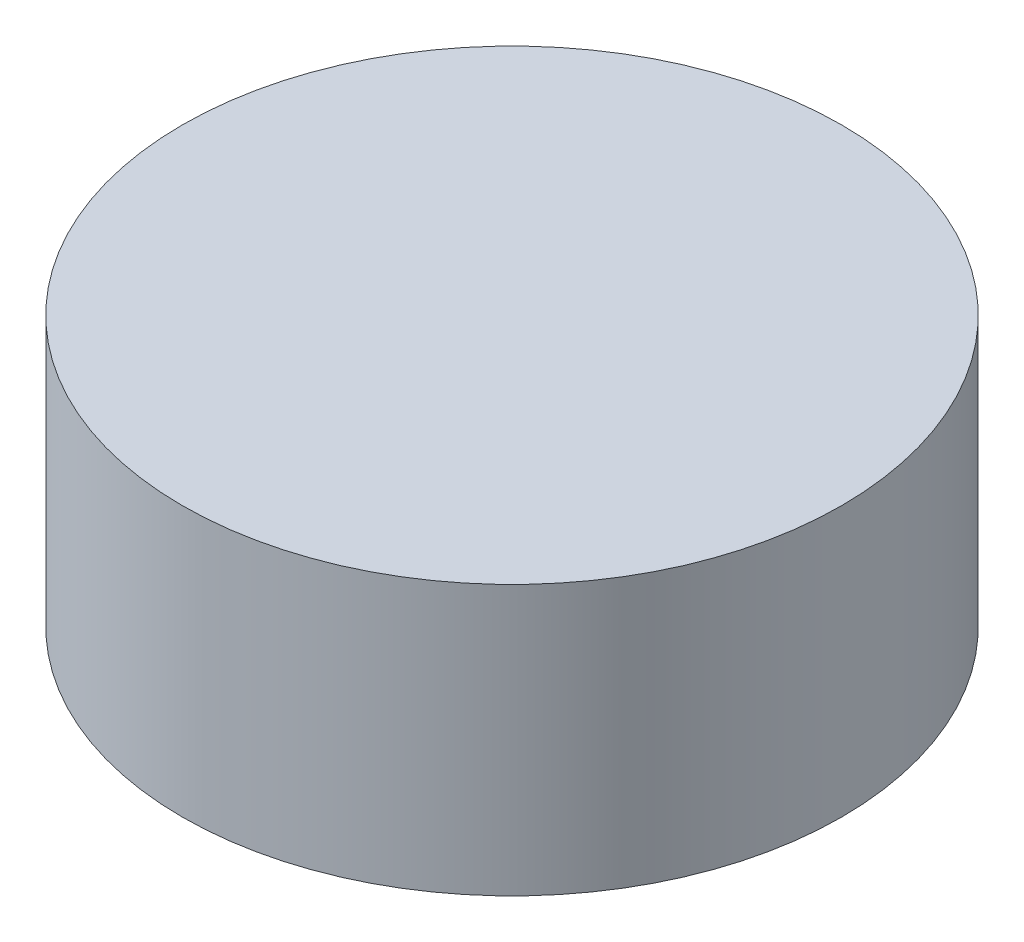
SolidWorks part; units mm, degrees
ref_plane "Front Plane" through (0, 0, 0) normal (0, 0, 1) x (1, 0, 0)
ref_plane "Top Plane" through (0, 0, 0) normal (0, 1, 0) x (1, 0, 0)
ref_plane "Right Plane" through (0, 0, 0) normal (1, 0, 0) x (0, 0, -1)
sketch "Sketch1" plane through (0, 0, 0) normal (0, 0, 1) x (1, 0, 0)
  line L0 (0, 4.5) -> (5.5, 4.5)
  line L1 (5.5, 4.5) -> (5.5, 0)
  line L2 (5.5, 0) -> (0, 0)
  line L3 (0, 0) -> (0, 4.5)
  line L4 (0, 0) -> (0, 4.5) construction
revolve "Revolve1" add sketch "Sketch1" angle 360 about L4 reverse direction yes
ref_plane "ANBAU XY" through (0, 0, 0) normal (0, -1, 0) x (-1, 0, 0)
ref_plane "ANBAU XZ" through (0, 0, 0) normal (0, 0, -1) x (-1, 0, 0)
ref_plane "ANBAU YZ" through (0, 0, 0) normal (1, 0, 0) x (0, 0, -1)
ref_axis "ANBAU X" through (-80.9, 0, 0) along (1, 0, 0)
ref_axis "ANBAU Y" through (0, 0, -50) along (0, 0, 1)
ref_axis "ANBAU Z" through (0, -50, 0) along (0, 1, 0)
sketch3d "ANBAU"
  point P0 (0, 0, 0)
other "Freeze***"
